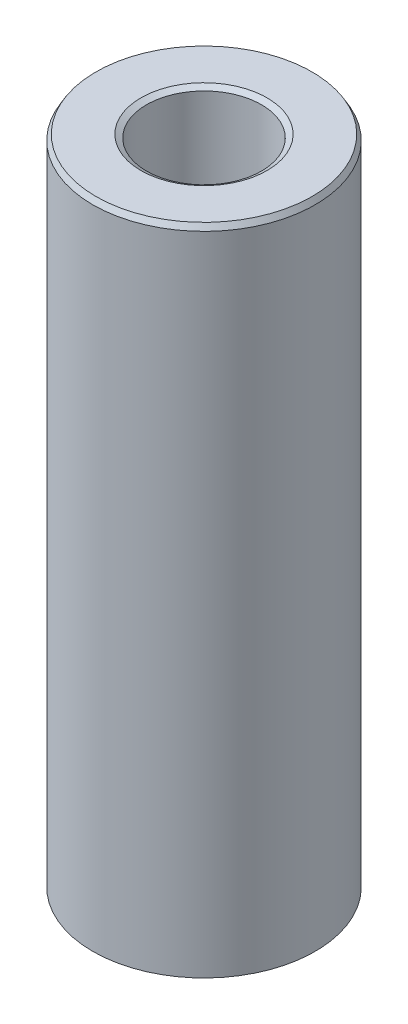
SolidWorks part; units mm, degrees
ref_plane "Front Plane" through (0, 0, 0) normal (0, 0, 1) x (1, 0, 0)
ref_plane "Top Plane" through (0, 0, 0) normal (0, 1, 0) x (1, 0, 0)
ref_plane "Right Plane" through (0, 0, 0) normal (1, 0, 0) x (0, 0, -1)
sketch "Sketch1" plane through (0, 0, 0) normal (0, 1, 0) x (1, 0, 0)
  circle A0 centre (0, 0) radius 52.5
  dimension "SLEEVE_OD" = 105
extrude "Boss-Extrude1" add sketch "Sketch1" along normal blind 309.3672
sketch "Sketch2" plane through (0, 0, 0) normal (0, 1, 0) x (1, 0, 0)
  circle A0 centre (0, 0) radius 27.1449
  dimension "BORE_D" = 54.2899
extrude "Cut-Extrude1" cut sketch "Sketch2" along normal through all
chamfer "Chamfer1" distance 2.6195 angle 30 4 edges at (0, 309.3672, 27.1449) (0, 0, 27.1449) (0, 0, 52.5) (0, 309.3672, 52.5) first distance on face at (0, 309.3672, 27.1449) first distance on face at (0, 0, 27.1449) first distance on face at (0, 309.3672, 52.5)
